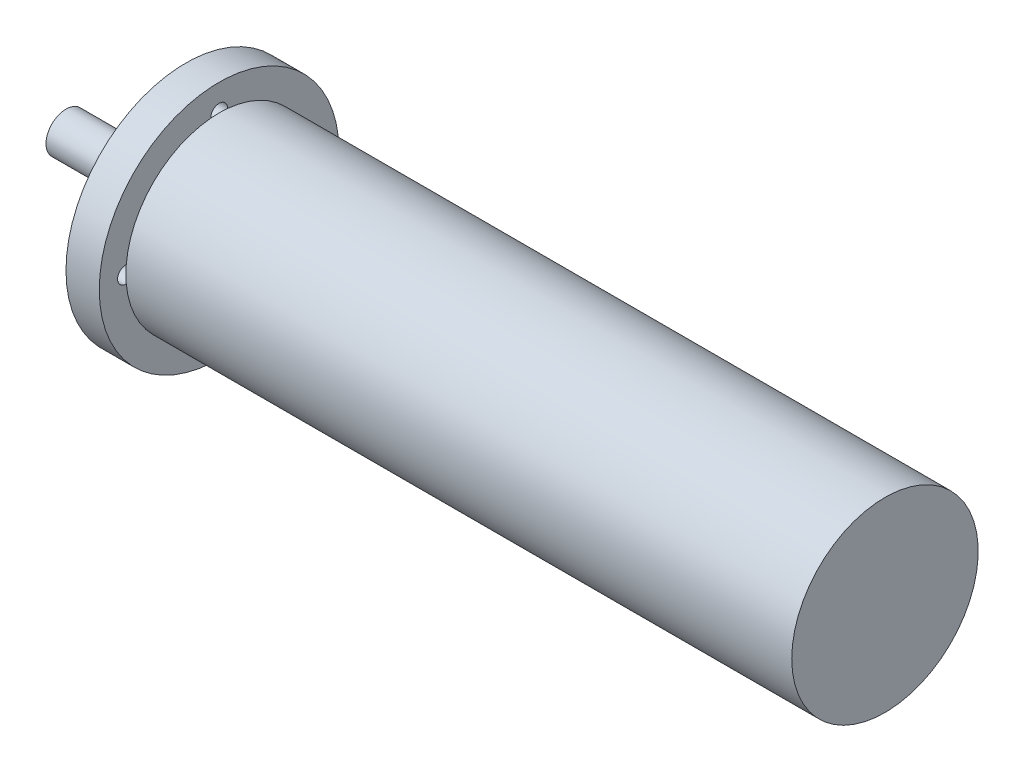
SolidWorks part; units mm, degrees
ref_plane "Plan de face" through (0, 0, 0) normal (0, 0, 1) x (1, 0, 0)
ref_plane "Plan de dessus" through (0, 0, 0) normal (0, 1, 0) x (1, 0, 0)
ref_plane "Plan de droite" through (0, 0, 0) normal (1, 0, 0) x (0, 0, -1)
sketch "Esquisse1" plane through (0, 0, 0) normal (0, 0, 1) x (1, 0, 0)
  line L0 (-16, 0) -> (0, 0) construction
  line L1 (0, 0) -> (123, 0)
  line L2 (123, 0) -> (123, 14)
  line L3 (123, 14) -> (23, 14)
  line L4 (23, 14) -> (23, 18)
  line L5 (23, 18) -> (18, 18)
  line L6 (18, 18) -> (18, 11)
  line L7 (18, 11) -> (16, 11)
  line L8 (16, 11) -> (16, 3)
  line L9 (16, 3) -> (0, 3)
  line L10 (0, 3) -> (0, 0)
  dimension "D1" = 6
  dimension "D2" = 22
  dimension "D3" = 36
  dimension "D4" = 28
  dimension "D5" = 18
  dimension "D6" = 2
  dimension "D7" = 5
  dimension "D8" = 105
revolve "Révolution1" add sketch "Esquisse1" angle 360 about L0
sketch "Esquisse2" plane through (18, 0, 0) normal (-1, 0, 0) x (0, 0, 1)
  circle A0 centre (0, 14) radius 1.25
  circle A1 centre (14, 0) radius 1.25
  circle A2 centre (0, -14) radius 1.25
  circle A3 centre (-14, 0) radius 1.25
  point P11 (0, 0)
  dimension "D1" = 4
  dimension "D2" = 28
  dimension "D3" = 2.5
extrude "Enlèv. mat.-Extru.1" cut sketch "Esquisse2" against normal up to surface (5 mm away) up to face at (23, 0, 18)
